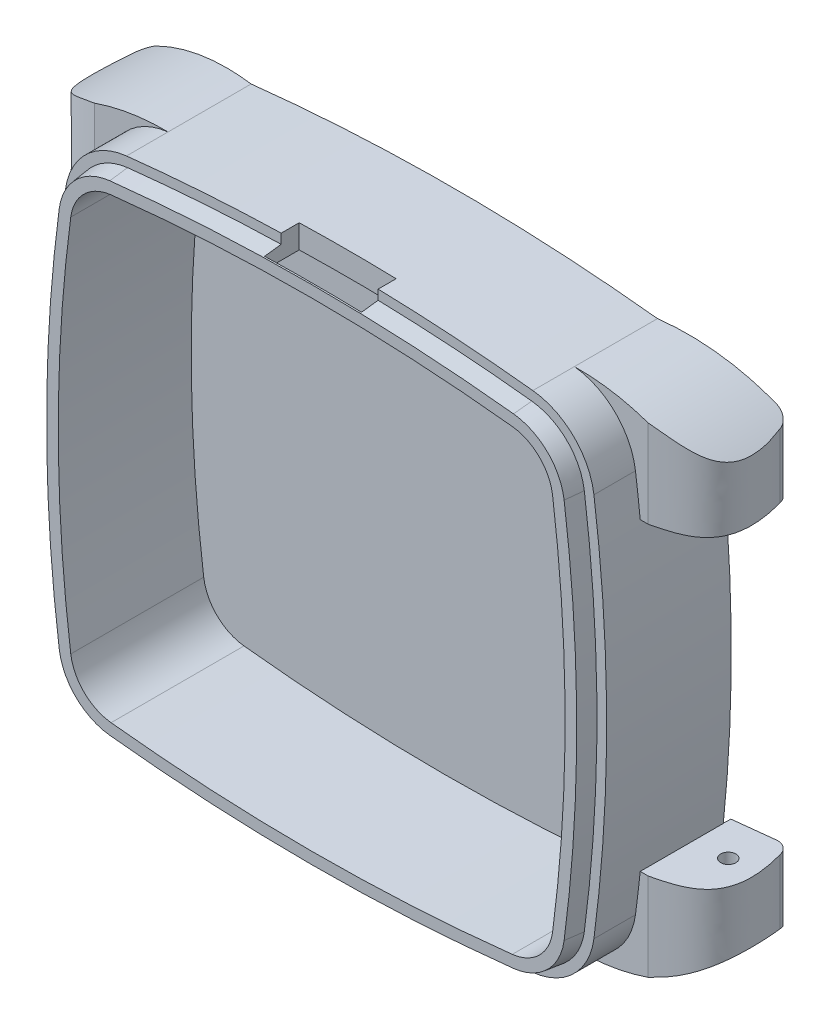
SolidWorks part; units mm, degrees
material "Özel Plastik"
ref_plane "Ön Düzlem" through (0, 0, 0) normal (0, 0, 1) x (1, 0, 0)
ref_plane "Üst Düzlem" through (0, 0, 0) normal (0, 1, 0) x (1, 0, 0)
ref_plane "Sağ Düzlem" through (0, 0, 0) normal (1, 0, 0) x (0, 0, -1)
sketch "Çizim1" plane through (0, 0, 0) normal (0, 0, 1) x (1, 0, 0)
  line L1 (-20, -19) -> (20, -19)
  line L2 (-20, -19) -> (-20, 19)
  line L3 (-20, 19) -> (20, 19)
  line L4 (20, -19) -> (20, 19)
  line L5 (-20, -19) -> (20, 19) construction
  line L6 (-20, 19) -> (20, -19) construction
  point P0 (0, 0)
  dimension "D1" = 40
  dimension "D2" = 38
extrude "Yükseklik-Ekstrüzyon1" add sketch "Çizim1" along normal mid plane 9 contours L3 L4 L1 L2
sketch "Çizim2" plane through (0, 0, 4.5) normal (0, 0, 1) x (1, 0, 0)
  line L0 (-20, 17.5) -> (20, 17.5) construction
  line L1 (-20, -19) -> (-20, 19) construction
  line L2 (20, -19) -> (20, 19) construction
  line L3 (-20, 19) -> (20, 19) construction
  line L4 (0, 0) -> (12.6557, 0) construction
  line L5 (-20, 19) -> (20, 19)
  line L6 (20, 19) -> (20, 17.5)
  line L7 (-20, 19) -> (-20, 17.5)
  line L8 (-20, -17.5) -> (20, -17.5) construction
  line L9 (-20, -19) -> (-20, -17.5)
  line L10 (20, -19) -> (20, -17.5)
  line L11 (-20, -19) -> (20, -19)
  arc A0 (-20, 17.5) -> (20, 17.5) centre (0, -115.0833) cw
  arc A1 (-20, -17.5) -> (20, -17.5) centre (0, 115.0833) ccw
  line M4 (-20, 19) -> (-20, -19)
  line M5 (-20, -19) -> (20, -19)
  line M6 (20, -19) -> (20, 19)
  line M7 (20, 19) -> (-20, 19)
  dimension "D1" = 1.5
extrude "Kes-Ekstrüzyon1" cut sketch "Çizim2" against normal through all contours A0 M7 M6 | A0 L5 M4 | A1 M4 M5 | A1 L11 M6 region at (-15.0056, 18.5504, 4.5) region at (15.0056, 18.5504, 4.5) region at (-15.0056, -18.5504, 4.5) region at (15.0056, -18.5504, 4.5)
sketch "Çizim3" plane through (0, 0, 4.5) normal (0, 0, 1) x (1, 0, 0)
  line L0 (18.5, 17.7176) -> (18.5, -17.7176) construction
  line L1 (20, -17.5) -> (20, 17.5) construction
  line L2 (20, 17.5) -> (20, -17.5)
  line L3 (0, 0) -> (0, -12.7146) construction
  line L4 (-18.5, 17.7176) -> (-18.5, -17.7176) construction
  line L5 (-20, 17.5) -> (-20, -17.5)
  arc A0 (20, 17.5) -> (-20, 17.5) centre (0, -115.0833) ccw construction
  arc A1 (-20, -17.5) -> (20, -17.5) centre (0, 115.0833) ccw construction
  arc A2 (18.5, 17.7176) -> (18.5, -17.7176) centre (-85.3879, 0) cw
  arc A3 (18.5, -17.7176) -> (20, -17.5) centre (0, 115.0833) ccw
  arc A4 (20, 17.5) -> (18.5, 17.7176) centre (0, -115.0833) ccw
  arc A5 (-20, 17.5) -> (-18.5, 17.7176) centre (0, -115.0833) cw
  arc A6 (-18.5, -17.7176) -> (-20, -17.5) centre (0, 115.0833) cw
  arc A7 (-18.5, 17.7176) -> (-18.5, -17.7176) centre (85.3879, 0) ccw
  arc M3 (-20, -17.5) -> (20, -17.5) centre (0, 115.0833) ccw
  line M4 (20, -17.5) -> (20, 17.5)
  arc M5 (20, 17.5) -> (-20, 17.5) centre (0, -115.0833) ccw
  line M6 (-20, 17.5) -> (-20, -17.5)
  dimension "D1" = 1.5
extrude "Kes-Ekstrüzyon2" cut sketch "Çizim3" against normal through all contours A2 L2 M5 | A2 M4 M3 | A7 L5 M3 | A7 M5 M6 region at (19.5514, 13.2137, 4.5) region at (19.5514, -13.2137, 4.5) region at (-19.5514, 13.2137, 4.5) region at (-19.5514, -13.2137, 4.5)
fillet "Radyus1" radius 5 4 edges at (-18.5, -17.7176, 0) (18.5, -17.7176, 0) (-18.5, 17.7176, 0) (18.5, 17.7176, 0)
shell "İç Boşaltma1" thickness 0.7 removed face at (0, 0, 4.5)
sketch "Çizim4" plane through (0, 0, -3.8) normal (0, 0, 1) x (1, 0, 0)
  arc A16 (-14.4862, -16.505) -> (14.4862, -16.505) centre (0, 115.0833) ccw
  arc A17 (14.4862, -16.505) -> (17.3963, -13.6596) centre (14.1251, -13.2248) ccw
  arc A18 (17.3963, -13.6596) -> (17.3963, 13.6596) centre (-85.3879, 0) ccw
  arc A19 (17.3963, 13.6596) -> (14.4862, 16.505) centre (14.1251, 13.2248) ccw
  arc A20 (14.4862, 16.505) -> (-14.4862, 16.505) centre (0, -115.0833) ccw
  arc A21 (-14.4862, 16.505) -> (-17.3963, 13.6596) centre (-14.1251, 13.2248) ccw
  arc A22 (-17.3963, 13.6596) -> (-17.3963, -13.6596) centre (85.3879, 0) ccw
  arc A23 (-17.3963, -13.6596) -> (-14.4862, -16.505) centre (-14.1251, -13.2248) ccw
  arc A24 (-14.4862, -16.505) -> (14.4862, -16.505) centre (0, 115.0833) ccw
  arc A25 (14.4862, -16.505) -> (17.3963, -13.6596) centre (14.1251, -13.2248) ccw
  arc A26 (17.3963, -13.6596) -> (17.3963, 13.6596) centre (-85.3879, 0) ccw
  arc A27 (17.3963, 13.6596) -> (14.4862, 16.505) centre (14.1251, 13.2248) ccw
  arc A28 (14.4862, 16.505) -> (-14.4862, 16.505) centre (0, -115.0833) ccw
  arc A29 (-14.4862, 16.505) -> (-17.3963, 13.6596) centre (-14.1251, 13.2248) ccw
  arc A30 (-17.3963, 13.6596) -> (-17.3963, -13.6596) centre (85.3879, 0) ccw
  arc A31 (-17.3963, -13.6596) -> (-14.4862, -16.505) centre (-14.1251, -13.2248) ccw
  arc A32 (-14.5956, -17.499) -> (14.5956, -17.499) centre (0, 115.0833) ccw
  arc A33 (14.5956, -17.499) -> (18.3876, -13.7913) centre (14.1251, -13.2248) ccw
  arc A34 (18.3876, -13.7913) -> (18.3876, 13.7913) centre (-85.3879, 0) ccw
  arc A35 (18.3876, 13.7913) -> (14.5956, 17.499) centre (14.1251, 13.2248) ccw
  arc A36 (14.5956, 17.499) -> (-14.5956, 17.499) centre (0, -115.0833) ccw
  arc A37 (-14.5956, 17.499) -> (-18.3876, 13.7913) centre (-14.1251, 13.2248) ccw
  arc A38 (-18.3876, 13.7913) -> (-18.3876, -13.7913) centre (85.3879, 0) ccw
  arc A39 (-18.3876, -13.7913) -> (-14.5956, -17.499) centre (-14.1251, -13.2248) ccw
  arc A40 (-14.5956, -17.499) -> (14.5956, -17.499) centre (0, 115.0833) ccw
  arc A41 (14.5956, -17.499) -> (18.3876, -13.7913) centre (14.1251, -13.2248) ccw
  arc A42 (18.3876, -13.7913) -> (18.3876, 13.7913) centre (-85.3879, 0) ccw
  arc A43 (18.3876, 13.7913) -> (14.5956, 17.499) centre (14.1251, 13.2248) ccw
  arc A44 (14.5956, 17.499) -> (-14.5956, 17.499) centre (0, -115.0833) ccw
  arc A45 (-14.5956, 17.499) -> (-18.3876, 13.7913) centre (-14.1251, 13.2248) ccw
  arc A46 (-18.3876, 13.7913) -> (-18.3876, -13.7913) centre (85.3879, 0) ccw
  arc A47 (-18.3876, -13.7913) -> (-14.5956, -17.499) centre (-14.1251, -13.2248) ccw
  dimension "D2" = 0
  dimension "D1" = 1
extrude "Yükseklik-Ekstrüzyon2" add sketch "Çizim4" along normal blind 9.6
sketch "Çizim7" plane through (0, 0, -4.5) normal (0, 0, -1) x (-1, 0, 0)
  line L0 (25.5, 14) -> (25.5, -14)
  line L1 (0, 0) -> (0, 12.7906) construction
  line L2 (0, 0) -> (-9.1265, 0) construction
  line L3 (-25.5, 14) -> (-25.5, -14)
  arc A0 (14.6722, -18.1948) -> (19.0815, -13.8835) centre (14.1251, -13.2248) ccw construction
  arc A1 (19.0815, -13.8835) -> (19.0815, 13.8835) centre (-85.3879, 0) ccw construction
  arc A2 (19.0815, 13.8835) -> (14.6722, 18.1948) centre (14.1251, 13.2248) ccw construction
  arc A3 (14.6722, -18.1948) -> (19.0815, -13.8835) centre (14.1251, -13.2248) ccw
  arc A4 (19.0815, -13.8835) -> (19.0815, 13.8835) centre (-85.3879, 0) ccw
  arc A5 (19.0815, 13.8835) -> (14.6722, 18.1948) centre (14.1251, 13.2248) ccw
  arc A6 (14.6722, -18.1948) -> (25.5, -14) centre (14.9196, -2.7615) ccw
  arc A7 (14.6722, 18.1948) -> (25.5, 14) centre (14.9196, 2.7615) cw
  arc A8 (-14.6722, 18.1948) -> (-25.5, 14) centre (-14.9196, 2.7615) ccw
  arc A9 (-14.6722, -18.1948) -> (-25.5, -14) centre (-14.9196, -2.7615) cw
  arc A10 (-19.0815, 13.8835) -> (-14.6722, 18.1948) centre (-14.1251, 13.2248) cw
  arc A11 (-19.0815, -13.8835) -> (-19.0815, 13.8835) centre (85.3879, 0) cw
  arc A12 (-14.6722, -18.1948) -> (-19.0815, -13.8835) centre (-14.1251, -13.2248) cw
  point P5 (20, 0)
  dimension "D1" = 5.5
  dimension "D2" = 14
  dimension "D3" = 14
extrude "Yükseklik-Ekstrüzyon4" add sketch "Çizim7" against normal blind 6 and the other way blind 4
sketch "Çizim8" plane through (0, 0, 0) normal (0, 1, 0) x (1, 0, 0)
  line L0 (-14.6722, 4.5) -> (-14.6722, 8.5)
  line L1 (-27.9186, 10.7243) -> (-27.9186, -3)
  line L2 (-27.9186, -3) -> (-20, -1.5)
  line L3 (0, 4.5) -> (0, -13.103) construction
  line L4 (14.6722, 4.5) -> (-14.6722, 4.5) construction
  line L5 (27.9186, 10.7243) -> (14.6722, 8.5)
  line L6 (22.4335, 5.3905) -> (14.6722, 4.5)
  line L8 (27.9186, -3) -> (20, -1.5)
  line L9 (27.9186, 10.7243) -> (27.9186, -3)
  line L10 (-20, -1.5) -> (-19.0815, -1.5) construction
  line L13 (-22.4335, 5.3905) -> (-14.6722, 4.5)
  line L14 (-25.5, -1.5) -> (-14.6722, -1.5) construction
  line L15 (14.6722, 4.5) -> (14.6722, 8.5)
  line L18 (-27.9186, 10.7243) -> (-14.6722, 8.5)
  arc A0 (-23.4243, 4.6022) -> (-22.4335, 5.3905) centre (-22.4469, 4.3906) cw
  arc A1 (23.4243, 4.6022) -> (22.4335, 5.3905) centre (22.4469, 4.3906) ccw
  spline S0 degree 3 poles (-20, -1.5) (-22.4731, -0.9161) (-24.7458, -0.1559) (-23.4243, 4.6022) knots 0 0 0 0 0.893244 0.893244 0.893244 0.893244
  spline S1 degree 3 poles (20, -1.5) (22.4731, -0.9161) (24.7458, -0.1559) (23.4243, 4.6022) knots 0 0 0 0 0.893244 0.893244 0.893244 0.893244
  point P16 (-27.9186, 10.7243)
  point P18 (-20.1545, -1.5)
  point P20 (-20, -1.5)
extrude "Kes-Ekstrüzyon4" cut sketch "Çizim8" against normal blind 38 and the other way blind 28
fillet "Radyus3" radius 0.2 6 edges at (20, 0, -4.5) (-20, 0, -4.5) (17.6207, 16.7999, -4.5) (17.6207, -16.7999, -4.5) (-17.6207, 16.7999, -4.5) (-17.6207, -16.7999, -4.5)
sketch "Çizim9" plane through (0, 0, 0) normal (0, 0, 1) x (1, 0, 0)
  line L0 (0, 0) -> (0, 33.3031) construction
  line L1 (-19.4244, 11) -> (-29.4244, 11)
  line L2 (29.4244, 11) -> (29.4244, -11)
  line L3 (-19.4244, -11) -> (-29.4244, -11)
  line L4 (-29.4244, 11) -> (-29.4244, -11)
  line L5 (19.4244, -11) -> (29.4244, -11)
  line L6 (19.4244, 11) -> (29.4244, 11)
  arc A0 (-14.6722, -18.1948) -> (14.6722, -18.1948) centre (0, 115.0833) ccw construction
  arc A2 (-19.0815, 13.8835) -> (-19.0815, -13.8835) centre (85.3879, 0) ccw construction
  arc A3 (-19.4244, 11) -> (-19.4244, -11) centre (85.3879, 0) ccw
  arc A4 (19.4244, 11) -> (19.4244, -11) centre (-85.3879, 0) cw
  point P9 (0, -19)
  point P15 (-19.4244, 11)
  point P19 (0, 0)
  point P20 (-19.4244, -11)
  dimension "D1" = 8
  dimension "D2" = 10
  dimension "D5" = 22
extrude "Kes-Ekstrüzyon5" cut sketch "Çizim9" against normal blind 38 and the other way blind 38
sketch "Çizim12" plane through (0, 0, -4.5) normal (0, 0, -1) x (-1, 0, 0)
  line L0 (23.8131, -11) -> (20, -11) construction
  line L1 (-21.9066, 11) -> (20.7668, 11)
  line L2 (-21.9066, 11) -> (-21.9066, -11)
  line L3 (-21.9066, -11) -> (20.7668, -11)
  line L4 (20.7668, 11) -> (20.7668, -11)
  line L5 (-23.8131, 11) -> (-20, 11) construction
  point P6 (20.7668, -11)
  point P9 (-21.9066, 11)
extrude "Kes-Ekstrüzyon9" cut sketch "Çizim12" along normal blind 10
sketch "Çizim13" plane through (0, 11, 0) normal (0, -1, 0) x (-1, 0, 0)
  line L5 (19.0815, -4.5) -> (20, -4.5) construction
  line L7 (19.4244, -1.5) -> (19.4244, 4.5) construction
  line L8 (-20, -4.5) -> (-19.0815, -4.5) construction
  line L9 (-19.4244, -1.5) -> (-19.4244, 4.5) construction
  circle A0 centre (-21.7844, 2.5) radius 0.55
  circle A1 centre (21.7844, 2.5) radius 0.55
  dimension "D1" = 1.1
  dimension "D4" = 1.1
  dimension "D2" = 7
  dimension "D3" = 2.36
  dimension "D5" = 7
  dimension "D6" = 2.36
extrude "Kes-Ekstrüzyon10" cut sketch "Çizim13" along normal blind 23.25 and the other way blind 1.25
chamfer "Pah1" distance 1.3 angle 7 8 edges at (-17.1313, 16.2994, 5.8) (-19.3, 0, 5.8) (0, 18.3, 5.8) (-17.1313, -16.2994, 5.8) (17.1313, 16.2994, 5.8) (0, -18.3, 5.8) (19.3, 0, 5.8) (17.1313, -16.2994, 5.8) first distance on face at (-16.8114, 15.9723, 5.15) first distance on face at (-18.8438, 0, 5.15) first distance on face at (0, 17.8995, 5.15) first distance on face at (-16.8114, -15.9723, 5.15) first distance on face at (16.8114, 15.9723, 5.15) first distance on face at (0, -17.8995, 5.15) first distance on face at (18.8438, 0, 5.15) first distance on face at (16.8114, -15.9723, 5.15)
sketch "Çizim14" plane through (0, 0, 0) normal (0, 1, 0) x (1, 0, 0)
  line L1 (3.5, -5.7) -> (-3.5, -5.7)
  line L2 (3.5, -5.7) -> (3.5, -3.2)
  line L3 (3.5, -3.2) -> (-3.5, -3.2)
  line L4 (-3.5, -5.7) -> (-3.5, -3.2)
  line L5 (-14.6722, -4.5) -> (14.6722, -4.5) construction
  line L6 (-14.4862, 3.8) -> (14.4862, 3.8) construction
  point P6 (0, -4.5)
  dimension "D1" = 2.5
  dimension "D2" = 7
  dimension "D3" = 3.5
  dimension "D4" = 7
extrude "Kes-Ekstrüzyon11" cut sketch "Çizim14" along normal blind 40
